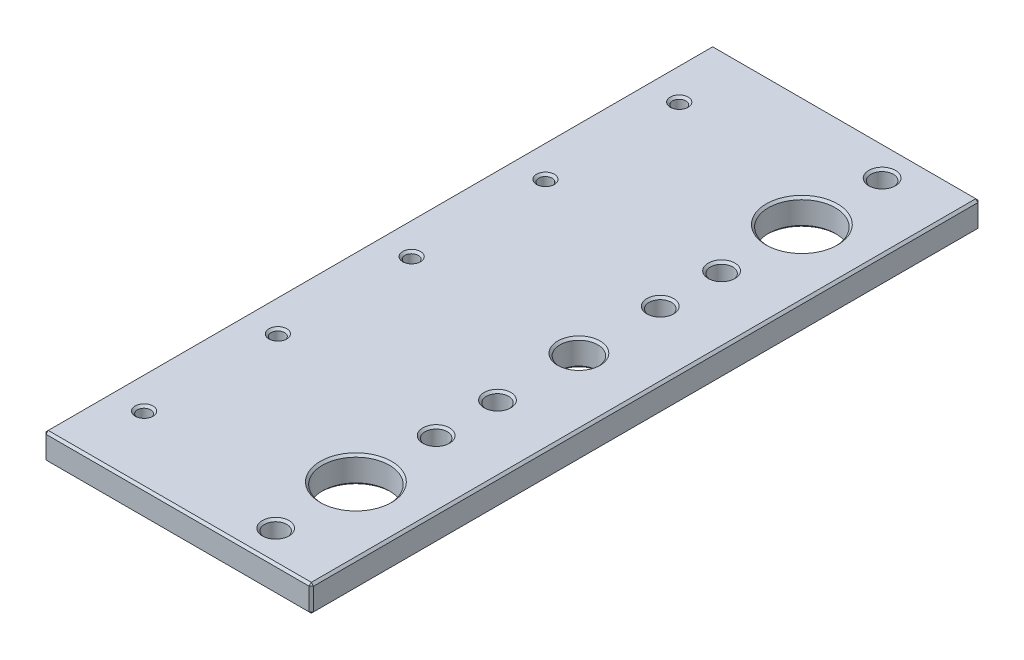
SolidWorks part; units mm, degrees
ref_plane "Alzado" through (0, 0, 0) normal (0, 0, 1) x (1, 0, 0)
ref_plane "Planta" through (0, 0, 0) normal (0, 1, 0) x (1, 0, 0)
ref_plane "Vista lateral" through (0, 0, 0) normal (1, 0, 0) x (0, 0, -1)
sketch "Croquis1" plane through (0, 0, 0) normal (0, 1, 0) x (1, 0, 0)
  line L0 (5.2717, 17.2086) -> (5.2717, -19.2914) construction
  line L1 (-39.7283, 73.9586) -> (20.2717, 73.9586)
  line L2 (-39.7283, 73.9586) -> (-39.7283, -76.0414)
  line L3 (-39.7283, -76.0414) -> (20.2717, -76.0414)
  line L4 (20.2717, 73.9586) -> (20.2717, -76.0414)
  circle A0 centre (-32.2283, 28.9586) radius 1.5
  circle A1 centre (-32.2283, -31.0414) radius 1.5
  circle A2 centre (5.2717, 17.2086) radius 2.5
  circle A3 centre (5.2717, -19.2914) radius 2.5
  circle A4 centre (-32.2283, 58.9586) radius 1.5
  circle A5 centre (-32.2283, -61.0414) radius 1.5
  circle A6 centre (5.2717, -1.0414) radius 4.25
  circle A7 centre (-32.2283, -1.0414) radius 1.5
  circle A8 centre (5.2717, -51.0414) radius 7.5
  circle A9 centre (5.2717, 48.9586) radius 7.5
  circle A10 centre (5.2717, 66.9586) radius 2.5
  circle A11 centre (5.2717, 30.9586) radius 2.5
  circle A12 centre (5.2717, -33.0414) radius 2.5
  circle A13 centre (5.2717, -69.0414) radius 2.5
  dimension "D7" = 30
  dimension "D8" = 3
  dimension "D9" = 3
  dimension "D10" = 37.5
  dimension "D11" = 15
  dimension "D12" = 36.5
  dimension "D17" = 75
  dimension "D16" = 8.5
  dimension "D19" = 3
  dimension "D20" = 15
  dimension "D21" = 15
  dimension "D24" = 5
  dimension "D25" = 5
  dimension "D28" = 5
  dimension "D29" = 5
  dimension "D4" = 3
  dimension "D5" = 3
  dimension "D18" = 5
  dimension "D32" = 5
  dimension "D1" = 150
  dimension "D6" = 30
  dimension "D13" = 15
  dimension "D14" = 7.5
  dimension "D15" = 15
  dimension "D22" = 50
  dimension "D23" = 50
  dimension "D26" = 18
  dimension "D27" = 18
  dimension "D30" = 18
  dimension "D31" = 18
extrude "Saliente-Extruir1" add sketch "Croquis1" along normal blind 6
chamfer "Chaflán1" distance 0.5 angle 45 40 edges at (-39.7283, 3, -73.9586) (-39.7283, 3, 76.0414) (20.2717, 3, 76.0414) (-9.7283, 0, 76.0414) (20.2717, 0, 1.0414) (-39.7283, 0, 1.0414) (-9.7283, 0, -73.9586) (20.2717, 3, -73.9586) (-9.7283, 6, -73.9586) (20.2717, 6, 1.0414) (-9.7283, 6, 76.0414) (-39.7283, 6, 1.0414) (-32.2283, 0, 62.5414) (-32.2283, 0, -57.4586) (-32.2283, 6, 62.5414) (-32.2283, 6, -57.4586) (5.2717, 0, 5.2914) (5.2717, 6, 5.2914) (5.2717, 0, -41.4586) (-32.2283, 0, 2.5414) (5.2717, 0, 58.5414) (5.2717, 6, -41.4586) (-32.2283, 6, 2.5414) (5.2717, 6, 58.5414) (5.2717, 0, 71.5414) (5.2717, 0, -28.4586) (5.2717, 0, -64.4586) (5.2717, 0, 35.5414) (5.2717, 6, 71.5414) (5.2717, 6, -28.4586) (5.2717, 6, -64.4586) (5.2717, 6, 35.5414) (-32.2283, 0, 32.5414) (-32.2283, 0, -27.4586) (-32.2283, 6, 32.5414) (-32.2283, 6, -27.4586) (5.2717, 0, 21.7914) (5.2717, 0, -14.7086) (5.2717, 6, 21.7914) (5.2717, 6, -14.7086)
